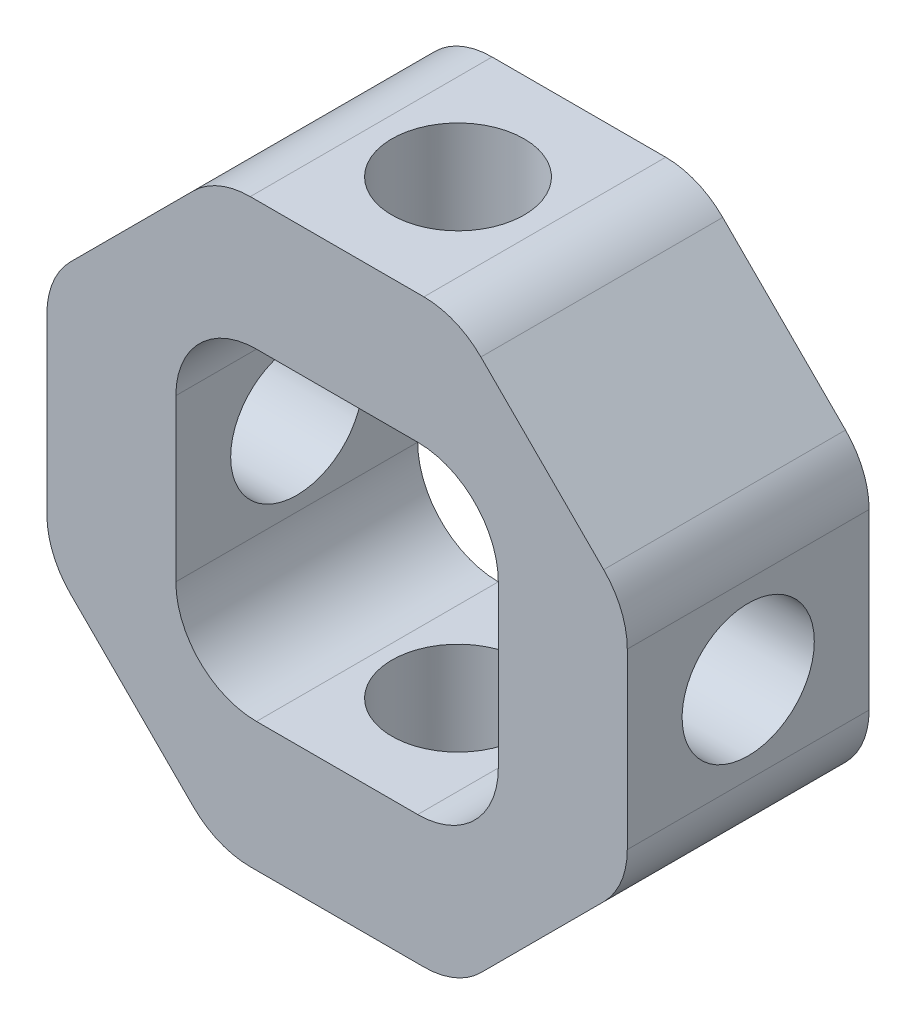
SolidWorks part; units mm, degrees
ref_plane "正面" through (0, 0, 0) normal (0, 0, 1) x (1, 0, 0)
ref_plane "平面" through (0, 0, 0) normal (0, 1, 0) x (1, 0, 0)
ref_plane "右側面" through (0, 0, 0) normal (1, 0, 0) x (0, 0, -1)
sketch "ｽｹｯﾁ1" plane through (0, 0, 0) normal (0, 0, 1) x (1, 0, 0)
  line L0 (7.4558, -18) -> (18, -7.4558)
  line L1 (-18, 7.4558) -> (-18, -7.4558)
  line L2 (-18, -7.4558) -> (-7.4558, -18)
  line L3 (-7.4558, -18) -> (7.4558, -18)
  line L4 (18, -7.4558) -> (18, 7.4558)
  line L5 (18, 7.4558) -> (7.4558, 18)
  line L6 (7.4558, 18) -> (-7.4558, 18)
  line L7 (-7.4558, 18) -> (-18, 7.4558)
  circle A0 centre (0, 0) radius 18 construction
  point P1 (0, -18)
  point P12 (-18, 0)
  dimension "D1" = 18
extrude "ﾎﾞｽ - 押し出し1" add sketch "ｽｹｯﾁ1" along normal mid plane 15
sketch "ｽｹｯﾁ2" plane through (0, 0, 7.5) normal (0, 0, 1) x (1, 0, 0)
  line L0 (7.4558, 18) -> (-7.4558, 18) construction
  line L1 (10, -10) -> (-10, -10)
  line L2 (10, -10) -> (10, 10)
  line L3 (10, 10) -> (-10, 10)
  line L4 (-10, -10) -> (-10, 10)
  line L5 (10, -10) -> (-10, 10) construction
  line L6 (10, 10) -> (-10, -10) construction
  line L7 (18, -7.4558) -> (18, 7.4558) construction
  point P0 (0, 0)
  dimension "D1" = 8
  dimension "D2" = 8
extrude "ｶｯﾄ - 押し出し1" cut sketch "ｽｹｯﾁ2" against normal through all both and the other way through all
fillet "ﾌｨﾚｯﾄ1" radius 5 4 edges at (10, -10, 0) (-10, -10, 0) (10, 10, 0) (-10, 10, 0)
fillet "ﾌｨﾚｯﾄ2" radius 5 8 edges at (18, -7.4558, 0) (7.4558, -18, 0) (-7.4558, -18, 0) (-18, -7.4558, 0) (18, 7.4558, 0) (7.4558, 18, 0) (-18, 7.4558, 0) (-7.4558, 18, 0)
sketch "ｽｹｯﾁ3" plane through (0, -18, 0) normal (0, -1, 0) x (1, 0, 0)
  circle A0 centre (0, 0) radius 4.1
  dimension "D1" = 8.2
extrude "ｶｯﾄ - 押し出し2" cut sketch "ｽｹｯﾁ3" against normal through all both and the other way through all
sketch "ｽｹｯﾁ4" plane through (18, 0, 0) normal (1, 0, 0) x (0, 0, -1)
  circle A0 centre (0, 0) radius 4.1
  dimension "D1" = 8.2
extrude "ｶｯﾄ - 押し出し3" cut sketch "ｽｹｯﾁ4" against normal through all both and the other way through all
